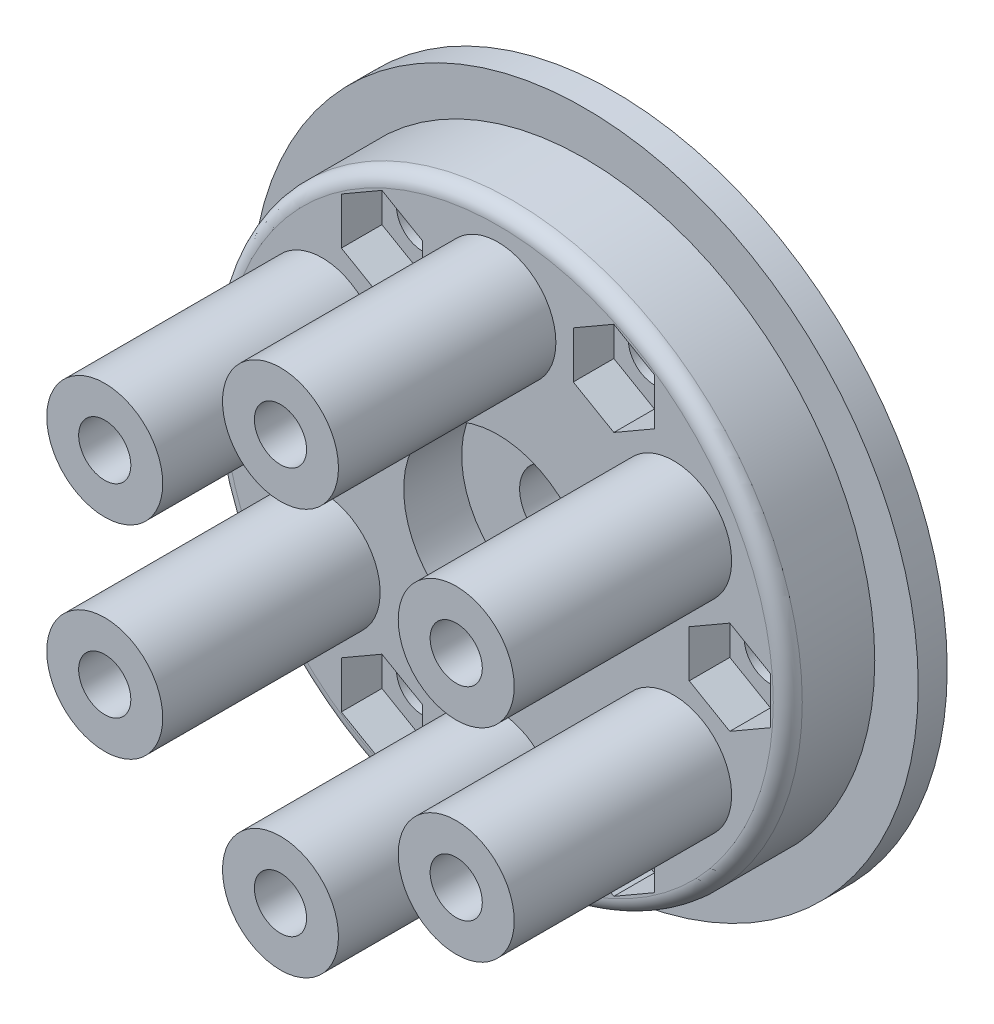
SolidWorks part; units mm, degrees
ref_plane "前视基准面" through (0, 0, 0) normal (0, 0, 1) x (1, 0, 0)
ref_plane "上视基准面" through (0, 0, 0) normal (0, 1, 0) x (1, 0, 0)
ref_plane "右视基准面" through (0, 0, 0) normal (1, 0, 0) x (0, 0, -1)
other "Configuration Table"
sketch "草图1" plane through (0, 0, 0) normal (0, 0, 1) x (1, 0, 0)
  circle A0 centre (0, 0) radius 14 construction
  circle A1 centre (0, 14) radius 4
  circle A2 centre (12.1244, 7) radius 4
  circle A3 centre (12.1244, -7) radius 4
  circle A4 centre (0, -14) radius 4
  circle A5 centre (-12.1244, -7) radius 4
  circle A6 centre (-12.1244, 7) radius 4
  point P17 (0, 0)
  dimension "D1" = 28
  dimension "D2" = 8
  dimension "D3" = 6
extrude "凸台-拉伸1" add sketch "草图1" along normal blind 20
sketch "草图2" plane through (0, 0, 0) normal (0, 0, -1) x (-1, 0, 0)
  circle A0 centre (0, 0) radius 20
  dimension "D1" = 40
extrude "凸台-拉伸2" add sketch "草图2" along normal blind 6
sketch "草图3" plane through (0, 0, 20) normal (0, 0, 1) x (1, 0, 0)
  circle A0 centre (0, 14) radius 1.8
  circle A1 centre (12.1244, 7) radius 1.8
  circle A2 centre (12.1244, -7) radius 1.8
  circle A3 centre (0, -14) radius 1.8
  circle A4 centre (-12.1244, -7) radius 1.8
  circle A5 centre (-12.1244, 7) radius 1.8
  circle A6 centre (0, 0) radius 14 construction
  point P15 (0, 0)
  dimension "D1" = 3.6
  dimension "D3" = 28
  dimension "D2" = 6
extrude "切除-拉伸1" cut sketch "草图3" against normal through all
sketch "草图4" plane through (0, 0, 0) normal (0, 0, 1) x (1, 0, 0)
  circle A0 centre (0, 0) radius 6.5
  dimension "D1" = 13
extrude "切除-拉伸2" cut sketch "草图4" against normal through all
sketch "草图5" plane through (0, 0, 0) normal (0, 0, 1) x (1, 0, 0)
  circle A0 centre (0, 0) radius 20
  circle A1 centre (0, 0) radius 23
  dimension "D1" = 46
extrude "凸台-拉伸3" add sketch "草图5" against normal blind 2
sketch "草图7" plane through (0, 0, 20) normal (0, 0, 1) x (1, 0, 0)
  circle A0 centre (0, -14) radius 4
  circle A1 centre (-12.1244, -7) radius 4
  circle A2 centre (-12.1244, 7) radius 4
  circle A3 centre (0, 14) radius 4
  circle A4 centre (12.1244, 7) radius 4
  circle A5 centre (12.1244, -7) radius 4
  circle A6 centre (-12.1244, -7) radius 4 construction
  point P15 (0, 0)
  dimension "D1" = 6
extrude "切除-拉伸3" cut sketch "草图7" against normal blind 5
sketch "草图8" plane through (0, 0, -6) normal (0, 0, -1) x (-1, 0, 0)
  circle A0 centre (0, 0) radius 2.5
  circle A1 centre (0, 0) radius 20
  circle A2 centre (12.1244, 7) radius 1.8 construction
  circle A3 centre (12.1244, 7) radius 1.8
  circle A4 centre (12.1244, -7) radius 1.8 construction
  circle A5 centre (0, -14) radius 1.8 construction
  circle A6 centre (-12.1244, -7) radius 1.8 construction
  circle A7 centre (-12.1244, 7) radius 1.8 construction
  circle A8 centre (0, 14) radius 1.8 construction
  circle A9 centre (12.1244, -7) radius 1.8
  circle A10 centre (0, -14) radius 1.8
  circle A11 centre (-12.1244, -7) radius 1.8
  circle A12 centre (-12.1244, 7) radius 1.8
  circle A13 centre (0, 14) radius 1.8
  dimension "D1" = 5
  dimension "D2" = 40
extrude "凸台-拉伸6" add sketch "草图8" along normal blind 4
sketch "草图12" plane through (0, 0, -10) normal (0, 0, -1) x (-1, 0, 0)
  circle A1 centre (0, 14) radius 3
  circle A3 centre (0, 0) radius 14 construction
  circle A4 centre (12.1244, 7) radius 3
  circle A5 centre (12.1244, -7) radius 3
  circle A6 centre (0, -14) radius 3
  circle A7 centre (-12.1244, -7) radius 3
  circle A8 centre (-12.1244, 7) radius 3
  point P19 (0, 0)
  dimension "D1" = 28
  dimension "D2" = 6
  dimension "D3" = 6
extrude "切除-拉伸4" cut sketch "草图12" against normal blind 3
sketch "草图13" plane through (0, 0, 0) normal (0, 0, 1) x (1, 0, 0)
  line L0 (16, 3.2332) -> (16, -3.2332) construction
  line L1 (16, 3.2332) -> (13.2, 1.6166)
  line L2 (13.2, 1.6166) -> (13.2, -1.6166)
  line L3 (13.2, -1.6166) -> (16, -3.2332)
  line L4 (16, -3.2332) -> (18.8, -1.6166)
  line L5 (18.8, -1.6166) -> (18.8, 1.6166)
  line L6 (18.8, 1.6166) -> (16, 3.2332)
  line L7 (10.8, -12.2398) -> (8, -10.6232)
  line L8 (8, -10.6232) -> (5.2, -12.2398)
  line L9 (5.2, -12.2398) -> (5.2, -15.473)
  line L10 (5.2, -15.473) -> (8, -17.0896)
  line L11 (8, -17.0896) -> (10.8, -15.473)
  line L12 (10.8, -15.473) -> (10.8, -12.2398)
  line L13 (10.8, -12.2398) -> (5.2, -15.473) construction
  line L14 (-5.2, -15.473) -> (-5.2, -12.2398)
  line L15 (-5.2, -12.2398) -> (-8, -10.6232)
  line L16 (-8, -10.6232) -> (-10.8, -12.2398)
  line L17 (-10.8, -12.2398) -> (-10.8, -15.473)
  line L18 (-10.8, -15.473) -> (-8, -17.0896)
  line L19 (-8, -17.0896) -> (-5.2, -15.473)
  line L20 (-5.2, -15.473) -> (-10.8, -12.2398) construction
  line L21 (-16, -3.2332) -> (-13.2, -1.6166)
  line L22 (-13.2, -1.6166) -> (-13.2, 1.6166)
  line L23 (-13.2, 1.6166) -> (-16, 3.2332)
  line L24 (-16, 3.2332) -> (-18.8, 1.6166)
  line L25 (-18.8, 1.6166) -> (-18.8, -1.6166)
  line L26 (-18.8, -1.6166) -> (-16, -3.2332)
  line L27 (-16, -3.2332) -> (-16, 3.2332) construction
  line L28 (-10.8, 12.2398) -> (-8, 10.6232)
  line L29 (-8, 10.6232) -> (-5.2, 12.2398)
  line L30 (-5.2, 12.2398) -> (-5.2, 15.473)
  line L31 (-5.2, 15.473) -> (-8, 17.0896)
  line L32 (-8, 17.0896) -> (-10.8, 15.473)
  line L33 (-10.8, 15.473) -> (-10.8, 12.2398)
  line L34 (-10.8, 12.2398) -> (-5.2, 15.473) construction
  line L35 (5.2, 15.473) -> (5.2, 12.2398)
  line L36 (5.2, 12.2398) -> (8, 10.6232)
  line L37 (8, 10.6232) -> (10.8, 12.2398)
  line L38 (10.8, 12.2398) -> (10.8, 15.473)
  line L39 (10.8, 15.473) -> (8, 17.0896)
  line L40 (8, 17.0896) -> (5.2, 15.473)
  line L41 (5.2, 15.473) -> (10.8, 12.2398) construction
  circle A0 centre (0, 0) radius 20 construction
  circle A1 centre (0, 0) radius 16 construction
  circle A2 centre (16, 0) radius 2.8 construction
  circle A3 centre (8, -13.8564) radius 2.8 construction
  circle A4 centre (-8, -13.8564) radius 2.8 construction
  circle A5 centre (-16, 0) radius 2.8 construction
  circle A6 centre (-8, 13.8564) radius 2.8 construction
  circle A7 centre (8, 13.8564) radius 2.8 construction
  point P54 (0, 0)
  dimension "D1" = 40
  dimension "D2" = 32
  dimension "D3" = 5.6
  dimension "D4" = 6
extrude "切除-拉伸5" cut sketch "草图13" against normal blind 2.8
sketch "草图14" plane through (0, 0, -2.8) normal (0, 0, 1) x (1, 0, 0)
  circle A0 centre (0, 0) radius 16 construction
  circle A1 centre (16, 0) radius 1.8
  circle A2 centre (8, -13.8564) radius 1.8
  circle A3 centre (-8, -13.8564) radius 1.8
  circle A4 centre (-16, 0) radius 1.8
  circle A5 centre (-8, 13.8564) radius 1.8
  circle A6 centre (8, 13.8564) radius 1.8
  point P17 (0, 0)
  dimension "D1" = 32
  dimension "D2" = 3.6
  dimension "D3" = 6
extrude "切除-拉伸6" cut sketch "草图14" against normal through all
sketch "草图15" plane through (0, 0, -10) normal (0, 0, -1) x (-1, 0, 0)
  circle A0 centre (0, 0) radius 2.5 construction
  circle A1 centre (0, 0) radius 20
  circle A2 centre (0, 0) radius 20
  circle A3 centre (0, 0) radius 2.5
  circle A4 centre (0, 14) radius 3 construction
  circle A5 centre (0, 14) radius 3
  circle A6 centre (-8, 13.8564) radius 1.8 construction
  circle A7 centre (-8, 13.8564) radius 1.8
  circle A8 centre (8, 13.8564) radius 1.8
  circle A9 centre (16, 0) radius 1.8
  circle A10 centre (8, -13.8564) radius 1.8
  circle A11 centre (-8, -13.8564) radius 1.8
  circle A12 centre (-16, 0) radius 1.8
  circle A13 centre (12.1244, 7) radius 3
  circle A14 centre (12.1244, -7) radius 3
  circle A15 centre (0, -14) radius 3
  circle A16 centre (-12.1244, -7) radius 3
  circle A17 centre (-12.1244, 7) radius 3
  point P23 (0, 0)
  point P34 (0, 0)
  dimension "D3" = 6
  dimension "D1" = 0
  dimension "D2" = 6
extrude "凸台-拉伸7" add sketch "草图15" along normal blind 1
sketch "草图16" plane through (0, 0, -7) normal (0, 0, -1) x (-1, 0, 0)
  circle A0 centre (0, -14) radius 1.8 construction
  circle A1 centre (0, -14) radius 3
  circle A2 centre (0, -14) radius 3
  circle A3 centre (0, -14) radius 1.8
  circle A4 centre (-12.1244, -7) radius 1.8
  circle A5 centre (-12.1244, 7) radius 1.8
  circle A6 centre (0, 14) radius 1.8
  circle A7 centre (12.1244, 7) radius 1.8
  circle A8 centre (12.1244, -7) radius 1.8
  circle A9 centre (-12.1244, -7) radius 3
  circle A10 centre (-12.1244, 7) radius 3
  circle A11 centre (0, 14) radius 3
  circle A12 centre (12.1244, 7) radius 3
  circle A13 centre (12.1244, -7) radius 3
  point P17 (0, 0)
  point P28 (0, 0)
  dimension "D3" = 6
  dimension "D1" = 0
  dimension "D2" = 6
extrude "凸台-拉伸8" add sketch "草图16" along normal blind 1
sketch "草图17" plane through (0, 0, -2) normal (0, 0, -1) x (-1, 0, 0)
  circle A0 centre (0, 0) radius 20
  circle A1 centre (0, 0) radius 23
  circle A2 centre (0, 0) radius 23
  dimension "D1" = 0
extrude "凸台-拉伸9" add sketch "草图17" along normal blind 2 from offset 4
sketch "草图18" plane through (0, 0, -2) normal (0, 0, -1) x (-1, 0, 0)
  circle A0 centre (0, 0) radius 20
  circle A1 centre (0, 0) radius 23
  circle A2 centre (0, 0) radius 23
  circle A3 centre (0, 0) radius 20 construction
  dimension "D1" = 0
extrude "切除-拉伸7" cut sketch "草图18" against normal blind 2
fillet "圆角3" radius 1 1 edges at (-20, 0, 0)
sketch "草图19" plane through (0, 0, -6) normal (0, 0, 1) x (1, 0, 0)
  circle A0 centre (0, 0) radius 2.5
  circle A1 centre (0, 0) radius 6.5
  circle A2 centre (0, 0) radius 6.5
  dimension "D1" = 0
extrude "凸台-拉伸10" add sketch "草图19" along normal blind 2
sketch "草图21" plane through (0, 0, -11) normal (0, 0, -1) x (-1, 0, 0)
  circle A0 centre (0, 0) radius 20
extrude "切除-拉伸8" cut sketch "草图21" against normal blind 2
sketch "草图22" plane through (0, 0, -8) normal (0, 0, -1) x (-1, 0, 0)
  circle A0 centre (0, 14) radius 3
  circle A1 centre (-12.1244, 7) radius 3
  circle A2 centre (-12.1244, 7) radius 3
  circle A3 centre (12.1244, 7) radius 3
  circle A4 centre (12.1244, -7) radius 3
  circle A5 centre (0, -14) radius 3
  circle A6 centre (-12.1244, -7) radius 3
  point P15 (0, 0)
  dimension "D2" = 6
  dimension "D1" = 0
extrude "切除-拉伸9" cut sketch "草图22" against normal blind 2
fillet "圆角4" radius 1 1 edges at (-20, 0, -8)
